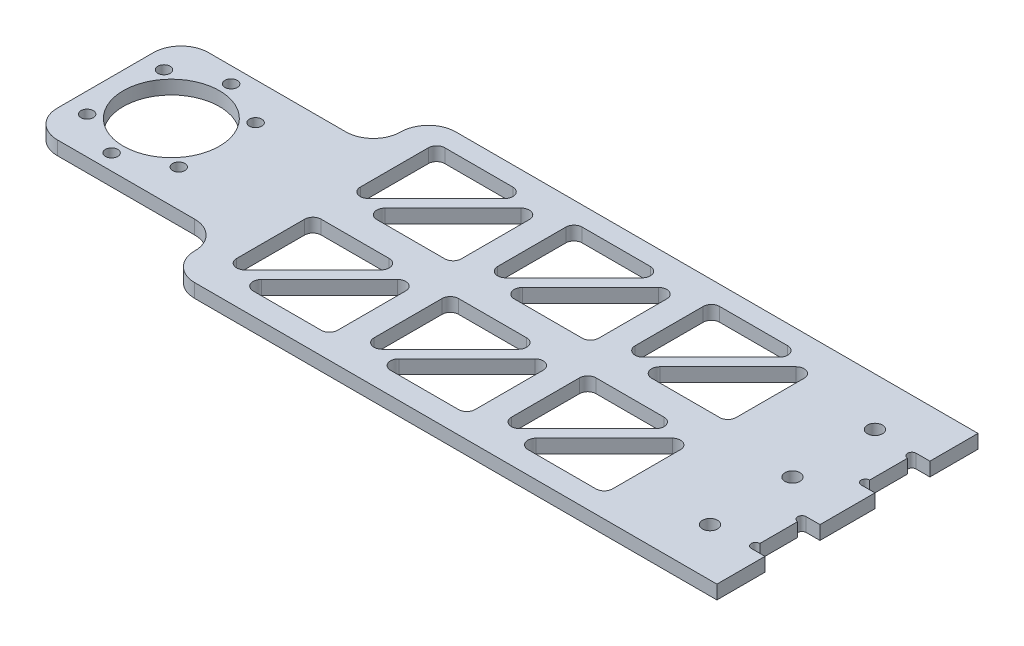
SolidWorks part; units mm, degrees
material "Hexcel AS4C (3000 丝)"
ref_plane "前视基准面" through (0, 0, 0) normal (0, 0, 1) x (1, 0, 0)
ref_plane "上视基准面" through (0, 0, 0) normal (0, 1, 0) x (1, 0, 0)
ref_plane "右视基准面" through (0, 0, 0) normal (1, 0, 0) x (0, 0, -1)
other "Configuration Table"
sketch "草图1" plane through (0, 0, 0) normal (0, 0, 1) x (1, 0, 0)
  line L0 (-270, 0) -> (0, 0)
  dimension "D1" = 270
extrude "拉伸-薄壁1" add sketch "草图1" along normal blind 95 thin thin type one direction wall 5
sketch "草图2" plane through (0, 0, 0) normal (0, 1, 0) x (1, 0, 0)
  line L0 (-241.9416, -47.5) -> (53.3701, -47.5) construction
  line L1 (-270, 0) -> (0, 0) construction
  line L2 (-270, -95) -> (0, -95) construction
  line L4 (-246, -47.5) -> (-246, 56.1187) construction
  line L5 (-246, -47.5) -> (-229.3385, -33.5194) construction
  line L7 (-270, -95) -> (-270, 0) construction
  circle A0 centre (-246, -47.5) radius 21.75 construction
  circle A2 centre (-246, -25.75) radius 2.25
  circle A3 centre (-229.3385, -33.5194) radius 2.25
  circle A4 centre (-262.6615, -33.5194) radius 2.25
  circle A5 centre (-262.6615, -61.4806) radius 2.25
  circle A6 centre (-246, -69.25) radius 2.25
  circle A7 centre (-229.3385, -61.4806) radius 2.25
  circle A17 centre (-246, -47.5) radius 17.5
  dimension "D1" = 24
  dimension "D2" = 43.5
  dimension "D4" = 4.5
  dimension "D9" = 35
  dimension "D5" = 50
extrude "切除-拉伸1" cut sketch "草图2" against normal blind 10
sketch "草图3" plane through (0, 0, 0) normal (0, 1, 0) x (1, 0, 0)
  line L0 (30.3557, -47.5) -> (-296.2486, -47.5) construction
  line L1 (-270, 0) -> (0, 0) construction
  line L2 (-270, -95) -> (0, -95) construction
  line L3 (-270, -75) -> (-200, -75)
  line L4 (-270, 0) -> (-200, 0)
  line L5 (-270, 0) -> (-270, -20)
  line L6 (-270, -20) -> (-200, -20)
  line L7 (-200, 0) -> (-200, -20)
  line L8 (-200, -95) -> (-200, -75)
  line L9 (-270, -95) -> (-200, -95)
  line L10 (-270, -95) -> (-270, -75)
  line L11 (-190, -10) -> (-190, -34.7574)
  line L12 (-184.8787, -36.8787) -> (-160.1213, -12.1213)
  line L13 (-162.2426, -7) -> (-187, -7)
  line L17 (-154.1213, -12.1213) -> (-178.8787, -36.8787)
  line L18 (-176.7574, -42) -> (-152, -42)
  line L19 (-149, -39) -> (-149, -14.2426)
  line L20 (-112.2426, -7) -> (-137, -7)
  line L21 (-140, -10) -> (-140, -34.7574)
  line L22 (-134.8787, -36.8787) -> (-110.1213, -12.1213)
  line L23 (-99, -39) -> (-99, -14.2426)
  line L24 (-104.1213, -12.1213) -> (-128.8787, -36.8787)
  line L25 (-126.7574, -42) -> (-102, -42)
  line L26 (-112.2426, -52) -> (-137, -52)
  line L27 (-140, -55) -> (-140, -79.7574)
  line L28 (-134.8787, -81.8787) -> (-110.1213, -57.1213)
  line L29 (-99, -84) -> (-99, -59.2426)
  line L30 (-104.1213, -57.1213) -> (-128.8787, -81.8787)
  line L31 (-126.7574, -87) -> (-102, -87)
  line L32 (-162.2426, -52) -> (-187, -52)
  line L33 (-190, -55) -> (-190, -79.7574)
  line L34 (-184.8787, -81.8787) -> (-160.1213, -57.1213)
  line L35 (-149, -84) -> (-149, -59.2426)
  line L36 (-154.1213, -57.1213) -> (-178.8787, -81.8787)
  line L37 (-176.7574, -87) -> (-152, -87)
  line L38 (-62.2426, -7) -> (-87, -7)
  line L39 (-90, -10) -> (-90, -34.7574)
  line L40 (-84.8787, -36.8787) -> (-60.1213, -12.1213)
  line L41 (-49, -39) -> (-49, -14.2426)
  line L42 (-54.1213, -12.1213) -> (-78.8787, -36.8787)
  line L43 (-76.7574, -42) -> (-52, -42)
  line L44 (-62.2426, -52) -> (-87, -52)
  line L45 (-90, -55) -> (-90, -79.7574)
  line L46 (-84.8787, -81.8787) -> (-60.1213, -57.1213)
  line L47 (-49, -84) -> (-49, -59.2426)
  line L48 (-54.1213, -57.1213) -> (-78.8787, -81.8787)
  line L49 (-76.7574, -87) -> (-52, -87)
  arc A0 (-190, -10) -> (-187, -7) centre (-187, -10) cw
  arc A1 (-152, -42) -> (-149, -39) centre (-152, -39) ccw
  arc A2 (-176.7574, -42) -> (-178.8787, -36.8787) centre (-176.7574, -39) cw
  arc A3 (-149, -14.2426) -> (-154.1213, -12.1213) centre (-152, -14.2426) ccw
  arc A4 (-160.1213, -12.1213) -> (-162.2426, -7) centre (-162.2426, -10) ccw
  arc A5 (-184.8787, -36.8787) -> (-190, -34.7574) centre (-187, -34.7574) cw
  arc A6 (-110.1213, -12.1213) -> (-112.2426, -7) centre (-112.2426, -10) ccw
  arc A7 (-140, -10) -> (-137, -7) centre (-137, -10) cw
  arc A8 (-134.8787, -36.8787) -> (-140, -34.7574) centre (-137, -34.7574) cw
  arc A9 (-99, -14.2426) -> (-104.1213, -12.1213) centre (-102, -14.2426) ccw
  arc A10 (-102, -42) -> (-99, -39) centre (-102, -39) ccw
  arc A11 (-126.7574, -42) -> (-128.8787, -36.8787) centre (-126.7574, -39) cw
  arc A12 (-110.1213, -57.1213) -> (-112.2426, -52) centre (-112.2426, -55) ccw
  arc A13 (-140, -55) -> (-137, -52) centre (-137, -55) cw
  arc A14 (-134.8787, -81.8787) -> (-140, -79.7574) centre (-137, -79.7574) cw
  arc A15 (-99, -59.2426) -> (-104.1213, -57.1213) centre (-102, -59.2426) ccw
  arc A16 (-102, -87) -> (-99, -84) centre (-102, -84) ccw
  arc A17 (-126.7574, -87) -> (-128.8787, -81.8787) centre (-126.7574, -84) cw
  arc A18 (-160.1213, -57.1213) -> (-162.2426, -52) centre (-162.2426, -55) ccw
  arc A19 (-190, -55) -> (-187, -52) centre (-187, -55) cw
  arc A20 (-184.8787, -81.8787) -> (-190, -79.7574) centre (-187, -79.7574) cw
  arc A21 (-149, -59.2426) -> (-154.1213, -57.1213) centre (-152, -59.2426) ccw
  arc A22 (-152, -87) -> (-149, -84) centre (-152, -84) ccw
  arc A23 (-176.7574, -87) -> (-178.8787, -81.8787) centre (-176.7574, -84) cw
  arc A24 (-90, -10) -> (-87, -7) centre (-87, -10) cw
  arc A25 (-84.8787, -36.8787) -> (-90, -34.7574) centre (-87, -34.7574) cw
  arc A26 (-60.1213, -12.1213) -> (-62.2426, -7) centre (-62.2426, -10) ccw
  arc A27 (-49, -14.2426) -> (-54.1213, -12.1213) centre (-52, -14.2426) ccw
  arc A28 (-76.7574, -42) -> (-78.8787, -36.8787) centre (-76.7574, -39) cw
  arc A29 (-52, -42) -> (-49, -39) centre (-52, -39) ccw
  arc A30 (-90, -55) -> (-87, -52) centre (-87, -55) cw
  arc A31 (-84.8787, -81.8787) -> (-90, -79.7574) centre (-87, -79.7574) cw
  arc A32 (-60.1213, -57.1213) -> (-62.2426, -52) centre (-62.2426, -55) ccw
  arc A33 (-49, -59.2426) -> (-54.1213, -57.1213) centre (-52, -59.2426) ccw
  arc A34 (-76.7574, -87) -> (-78.8787, -81.8787) centre (-76.7574, -84) cw
  arc A35 (-52, -87) -> (-49, -84) centre (-52, -84) ccw
  point P20 (-190, -7)
  point P29 (-149, -42)
  point P32 (-184, -42)
  point P35 (-149, -7)
  point P38 (-155, -7)
  point P41 (-190, -42)
  dimension "D10" = 3
  dimension "D1" = 20
  dimension "D2" = 70
  dimension "D3" = 35
  dimension "D4" = 35
  dimension "D5" = 7
  dimension "D6" = 10
  dimension "D7" = 35
  dimension "D8" = 35
  dimension "D9" = 6
  dimension "D13" = 9
  dimension "D14" = 10
  dimension "D16" = 9
  dimension "D11" = 2
  dimension "D12" = 2
  dimension "D15" = 2
extrude "切除-拉伸2" cut sketch "草图3" against normal blind 10
fillet "圆角1" radius 10 6 edges at (-200, -2.5, 95) (-200, -2.5, 0) (-200, -2.5, 20) (-200, -2.5, 75) (-270, -2.5, 75) (-270, -2.5, 20)
sketch "草图4" plane through (0, 0, 0) normal (0, 1, 0) x (1, 0, 0)
  line L0 (-20, 34.8204) -> (-20, -141.9637) construction
  line L1 (-304.2842, -47.5) -> (38.0342, -47.5) construction
  line L2 (-190, 0) -> (0, 0) construction
  line L3 (-190, -95) -> (0, -95) construction
  line L4 (0, -95) -> (0, 0) construction
  line L5 (-5, -57.5) -> (0, -57.5)
  line L6 (-5, -17.5) -> (0, -17.5)
  line L7 (-5, -17.5) -> (-5, -37.5)
  line L8 (-5, -37.5) -> (0, -37.5)
  line L9 (0, -17.5) -> (0, -37.5)
  line L10 (0, -77.5) -> (0, -57.5)
  line L11 (-5, -77.5) -> (0, -77.5)
  line L12 (-5, -77.5) -> (-5, -57.5)
  circle A0 centre (-20, -17.5) radius 2.75
  circle A1 centre (-20, -47.5) radius 2.75
  circle A2 centre (-20, -77.5) radius 2.75
  dimension "D1" = 5.5
  dimension "D2" = 60
  dimension "D3" = 20
  dimension "D4" = 20
  dimension "D5" = 5
  dimension "D6" = 10
extrude "切除-拉伸3" cut sketch "草图4" against normal blind 10
sketch "草图5" plane through (0, 0, 0) normal (0, 1, 0) x (1, 0, 0)
  line L0 (-5, -17.5) -> (-5, -37.5) construction
  line L1 (-5, -57.5) -> (-5, -77.5) construction
  line L2 (0, -17.5) -> (-5, -17.5) construction
  line L3 (-5, -37.5) -> (0, -37.5) construction
  line L4 (0, -57.5) -> (-5, -57.5) construction
  line L5 (-5, -77.5) -> (0, -77.5) construction
  circle A0 centre (-5, -19.05) radius 1.55
  circle A1 centre (-5, -35.95) radius 1.55
  circle A2 centre (-5, -59.05) radius 1.55
  circle A3 centre (-5, -75.95) radius 1.55
  dimension "D1" = 3.1
extrude "切除-拉伸4" cut sketch "草图5" against normal blind 10
